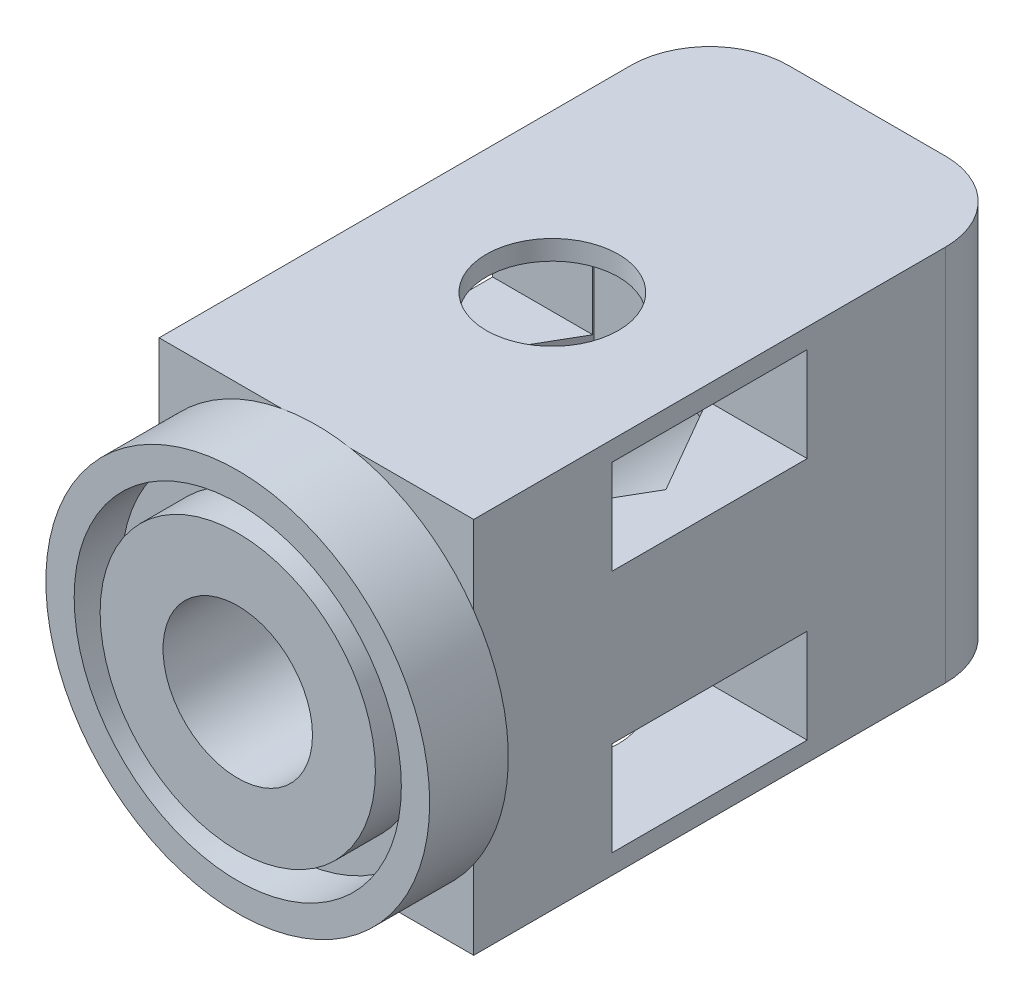
SolidWorks part; units mm, degrees
ref_plane "Front Plane" through (0, 0, 0) normal (0, 0, 1) x (1, 0, 0)
ref_plane "Top Plane" through (0, 0, 0) normal (0, 1, 0) x (1, 0, 0)
ref_plane "Right Plane" through (0, 0, 0) normal (1, 0, 0) x (0, 0, -1)
sketch "Sketch4" plane through (0, 0, 0) normal (0, 0, 1) x (1, 0, 0)
  line L0 (0, 0) -> (0, 11)
  line L1 (0, 0) -> (0, -11)
  line L3 (0, 11) -> (10, 11)
  line L4 (0, 11) -> (-10, 11)
  line L5 (0, -11) -> (-10, -11)
  line L6 (0, -11) -> (10, -11)
  line L7 (-10, 11) -> (-10, -11)
  line L8 (10, 11) -> (10, -11)
  line L9 (0, 11) -> (0, 5)
  circle A0 centre (0, 0) radius 4.75
  dimension "D4" = 9.5
  dimension "D1" = 11
  dimension "D2" = 11
  dimension "D3" = 10
  dimension "D5" = 6
extrude "Boss-Extrude2" add sketch "Sketch4" against normal blind 30 contours A0 L0 L4 L7 L5 L1 | A0 L1 L6 L8 L3 L0 region at (-5.573, 0, 0) region at (5.573, 0, 0)
sketch "Sketch7" plane through (0, -11, 0) normal (0, -1, 0) x (1, 0, 0)
  line L0 (0, 0) -> (0, -30)
  line L1 (10, -30) -> (-10, -30) construction
  circle A0 centre (0, -15) radius 4.2
  dimension "D1" = 8.4
extrude "Cut-Extrude1" cut sketch "Sketch7" against normal blind 30 contours L0 A0 | L0 A0 region at (1.7825, -11, -15) region at (-1.7825, -11, -15)
ref_plane "Plane1" through (0, 0, 0) normal (0, -1, 0) x (-1, 0, 0)
sketch "Sketch9" plane through (0, 0, 0) normal (0, -1, 0) x (-1, 0, 0)
  line L1 (7.2169, 15) -> (3.6084, 21.25)
  line L2 (3.6084, 21.25) -> (-3.6084, 21.25)
  line L3 (-3.6084, 21.25) -> (-7.2169, 15)
  line L4 (-7.2169, 15) -> (-3.6084, 8.75)
  line L5 (-3.6084, 8.75) -> (3.6084, 8.75)
  line L6 (3.6084, 8.75) -> (7.2169, 15)
  circle A0 centre (0, 15) radius 6.25 construction
  dimension "D1" = 12.5
sketch "Sketch11" plane through (0, -11, 0) normal (0, -1, 0) x (1, 0, 0)
  line L4 (10, 0) -> (-10, 0)
  line L5 (-10, 0) -> (-10, -30)
  line L6 (-10, -30) -> (10, -30)
  line L7 (10, -30) -> (10, 0)
  line L8 (10, 0) -> (-10, 0)
  line L9 (-10, 0) -> (-10, -30)
  line L10 (-10, -30) -> (10, -30)
  line L11 (10, -30) -> (10, 0)
  circle A0 centre (0, -15) radius 4.2 construction
  circle A1 centre (0, -15) radius 4.2
  dimension "D1" = 0
extrude "Boss-Extrude3" add sketch "Sketch11" along normal blind 1
sketch "Sketch12" plane through (0, 11, 0) normal (0, 1, 0) x (1, 0, 0)
  line L4 (-10, 0) -> (10, 0)
  line L5 (10, 0) -> (10, 30)
  line L6 (10, 30) -> (-10, 30)
  line L7 (-10, 30) -> (-10, 0)
  line L8 (-10, 0) -> (10, 0)
  line L9 (10, 0) -> (10, 30)
  line L10 (10, 30) -> (-10, 30)
  line L11 (-10, 30) -> (-10, 0)
  circle A0 centre (0, 15) radius 4.2 construction
  circle A1 centre (0, 15) radius 4.2
  dimension "D1" = 0
extrude "Boss-Extrude4" add sketch "Sketch12" along normal blind 1
extrude "Cut-Extrude2" cut sketch "Sketch9" against normal mid plane 21.5
sketch "Sketch16" plane through (0, 0, 0) normal (0, 0, 1) x (1, 0, 0)
  circle A0 centre (0, 0) radius 4.75
  circle A1 centre (0, 0) radius 10.2
  circle A2 centre (0, 0) radius 12.2
  dimension "D1" = 20.4
  dimension "D2" = 2
extrude "Boss-Extrude7" add sketch "Sketch16" along normal blind 2 contours A2
sketch "Sketch18" plane through (0, 0, 0) normal (0, 0, -1) x (-1, 0, 0)
  circle A1 centre (0, 0) radius 4.75
  circle A2 centre (0, 0) radius 4.75
  dimension "D1" = 0
extrude "Cut-Extrude3" cut sketch "Sketch18" against normal blind 2
sketch "Sketch19" plane through (0, 0, 2) normal (0, 0, 1) x (1, 0, 0)
  circle A0 centre (0, 0) radius 8.75
  circle A1 centre (0, 0) radius 12.2
  circle A2 centre (0, 0) radius 10.4
  circle M4 centre (0, 0) radius 4.75
  circle M5 centre (0, 0) radius 12.2
  dimension "D1" = 17.5
  dimension "D2" = 20.8
extrude "Boss-Extrude8" add sketch "Sketch19" along normal blind 3 contours A2 M5 | A0 M4 region at (-8.5025, 0, 2) region at (-11.8549, 0, 2)
sketch "Sketch21" plane through (0, 0, -30) normal (0, 0, -1) x (-1, 0, 0)
  line L4 (-10, 12) -> (-10, -12)
  line L5 (-10, -12) -> (10, -12)
  line L6 (10, -12) -> (10, 12)
  line L7 (10, 12) -> (-10, 12)
  line L8 (-10, 12) -> (-10, -12)
  line L9 (-10, -12) -> (10, -12)
  line L10 (10, -12) -> (10, 12)
  line L11 (10, 12) -> (-10, 12)
  circle A0 centre (0, 0) radius 4.75 construction
  circle A1 centre (0, 0) radius 4.75
  dimension "D1" = 0
extrude "Boss-Extrude9" add sketch "Sketch21" along normal blind 5
fillet "Fillet1" radius 5 2 edges at (10, 0, -35) (-10, 0, -35)
sketch "Sketch23" plane through (0, -12, 0) normal (0, -1, 0) x (1, 0, 0)
  line L0 (-4.2, -15) -> (-10, -15)
  line L1 (-10, 0) -> (-10, -30) construction
  circle A0 centre (0, -15) radius 4.2 construction
sketch "Sketch24" plane through (-10, 0, 0) normal (-1, 0, 0) x (0, 0, 1)
  line L0 (-15, -12) -> (-15, 12)
  line L1 (0, -12) -> (-30, -12) construction
  line L2 (-30, 12) -> (0, 12) construction
sketch "Sketch27" plane through (-10, 0, 0) normal (-1, 0, 0) x (0, 0, 1)
  line L0 (-15, -12) -> (-15, -10.75)
  line L1 (-15, -10.75) -> (-8.8, -10.75)
  line L2 (-15, -10.75) -> (-21.2, -10.75)
  line L3 (-8.8, -10.75) -> (-8.8, -4.75)
  line L4 (-8.8, -4.75) -> (-21.2, -4.75)
  line L5 (-21.2, -10.75) -> (-21.2, -4.75)
  line L6 (0, 0) -> (-3.8792, 0)
  line L7 (-21.2, 10.75) -> (-21.2, 4.75)
  line L8 (-8.8, 4.75) -> (-21.2, 4.75)
  line L9 (-8.8, 10.75) -> (-8.8, 4.75)
  line L10 (-15, 10.75) -> (-21.2, 10.75)
  line L11 (-15, 10.75) -> (-8.8, 10.75)
  line L12 (-15, 12) -> (-15, 10.75)
  dimension "D1" = 1.25
  dimension "D2" = 6.2
  dimension "D3" = 6.2
  dimension "D4" = 6
extrude "Cut-Extrude12" cut sketch "Sketch27" against normal through all both and the other way through all contours L11 L10 L7 L8 L9 | L5 L2 L1 L3 L4 region at (-10, -7.75, -15) region at (-10, 7.75, -15)
